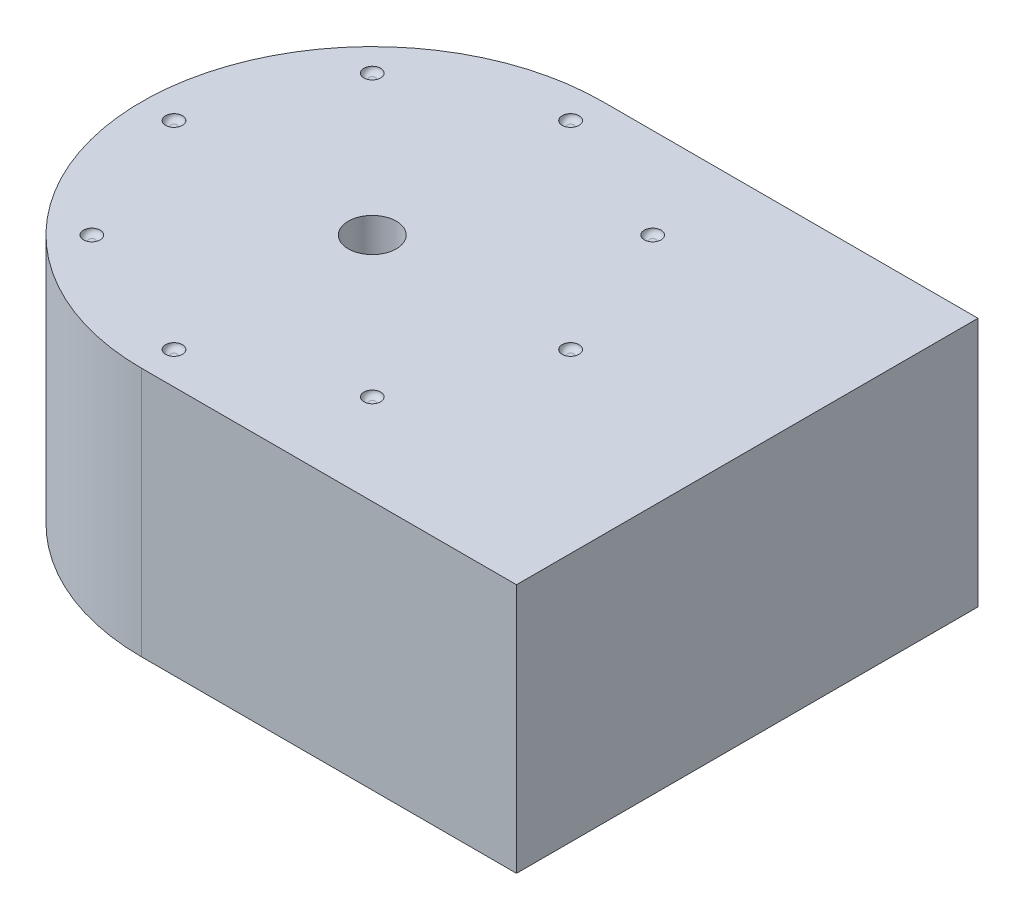
SolidWorks part; units mm, degrees
ref_plane "Alzado" through (0, 0, 0) normal (0, 0, 1) x (1, 0, 0)
ref_plane "Planta" through (0, 0, 0) normal (0, 1, 0) x (1, 0, 0)
ref_plane "Vista lateral" through (0, 0, 0) normal (1, 0, 0) x (0, 0, -1)
sketch "Croquis1" plane through (0, 0, 0) normal (0, 1, 0) x (1, 0, 0)
  line L0 (0, 0) -> (48, 0) construction
  line L1 (48, 0) -> (78, 0) construction
  line L2 (78, 0) -> (78, -48) construction
  line L4 (78, -48) -> (0, -48)
  line L5 (78, -48) -> (78, 48)
  line L6 (78, 48) -> (0, 48)
  line L7 (0, -48) -> (0, 48)
  circle A0 centre (0, 0) radius 48
extrude "Saliente-Extruir1" add sketch "Croquis1" along normal blind 52 contours L7 A0 | L7 A0 | A0 L4 L5 L6 region at (56.4256, 0, 0) region at (-20.3718, 0, 0) region at (20.3718, 0, 0)
sketch "Croquis2" plane through (0, 52, 0) normal (0, 1, 0) x (1, 0, 0)
  circle A0 centre (0, 0) radius 48
  circle A1 centre (0, 0) radius 43
  circle A2 centre (0, 0) radius 39.5
  circle A3 centre (0, 41.25) radius 1.75
  dimension "D1" = 79
extrude "Cortar-Extruir1" cut sketch "Croquis2" against normal blind 1.1 contours A3 | A3 region at (0, 52, -41.25)
fillet "Redondeo1" radius 1.1 1 edges at (0, 50.9, -39.5) type face fillet first side face at (0, 50.9, -39.5) second side face at (0, 50.9, -39.5)
pattern_circular "MatrizC3" count 8 over 360 about axis through (0, 52, 0) along (0, 1, 0) of "Redondeo1", "Cortar-Extruir1"
sketch "Croquis3" plane through (0, 52, 0) normal (0, 1, 0) x (1, 0, 0)
  circle A0 centre (0, 0) radius 5
extrude "Cortar-Extruir2" cut sketch "Croquis3" against normal blind 10
